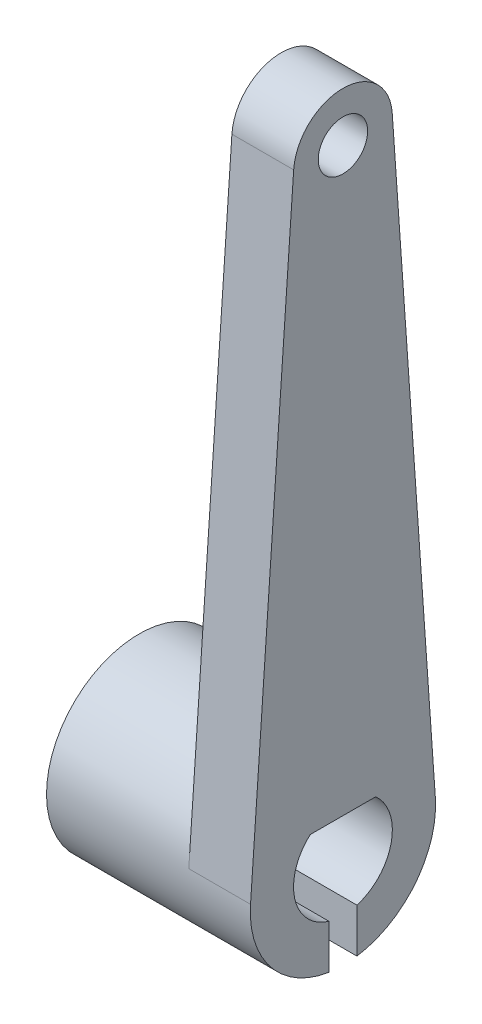
SolidWorks part; units mm, degrees
ref_plane "Front Plane" through (0, 0, 0) normal (0, 0, 1) x (1, 0, 0)
ref_plane "Top Plane" through (0, 0, 0) normal (0, 1, 0) x (1, 0, 0)
ref_plane "Right Plane" through (0, 0, 0) normal (1, 0, 0) x (0, 0, -1)
sketch "Sketch2" plane through (0, 0, 0) normal (1, 0, 0) x (0, 0, -1)
  line L0 (-2.6458, 3) -> (2.6458, 3)
  line L1 (-7.4816, 0.525) -> (-3.9902, 50.28)
  line L3 (3.9902, 50.28) -> (7.4816, 0.525)
  arc A0 (-2.6458, 3) -> (2.6458, 3) centre (0, 0) ccw
  arc A1 (-7.4816, 0.525) -> (7.4816, 0.525) centre (0, 0) ccw
  arc A2 (3.9902, 50.28) -> (-3.9902, 50.28) centre (0, 50) ccw
  circle A3 centre (0, 50) radius 2
  dimension "D1" = 8
  dimension "D2" = 7
  dimension "D3" = 15
  dimension "D4" = 8
  dimension "D6" = 4
  dimension "D5" = 50
extrude "Boss-Extrude1" add sketch "Sketch2" along normal blind 2.5 and the other way blind 2.5 contours L3 A2 L1 A1 A3 A0 L0 region at (0, 21.1681, 0)
sketch "Sketch3" plane through (2.5, 0, 0) normal (1, 0, 0) x (0, 0, -1)
  line L1 (-1.132, -11.1635) -> (1.132, -11.1635)
  line L2 (-1.132, -11.1635) -> (-1.132, -3.8365)
  line L3 (-1.132, -3.8365) -> (1.132, -3.8365)
  line L4 (1.132, -11.1635) -> (1.132, -3.8365)
  line L5 (-1.132, -11.1635) -> (1.132, -3.8365) construction
  line L6 (-1.132, -3.8365) -> (1.132, -11.1635) construction
  arc A0 (-7.4816, 0.525) -> (7.4816, 0.525) centre (0, 0) ccw construction
  arc A1 (-2.6458, 3) -> (2.6458, 3) centre (0, 0) ccw construction
  point P0 (0, -7.5)
extrude "Cut-Extrude1" cut sketch "Sketch3" against normal up to next
chamfer "Chamfer1" [suppressed] distance 0.5 angle 45
sketch "Sketch5" plane through (-2.5, 0, 0) normal (-1, 0, 0) x (0, 0, 1)
  line L5 (-1.132, -7.4141) -> (-1.132, -3.8365)
  line L6 (-2.6458, 3) -> (2.6458, 3)
  line L7 (1.132, -3.8365) -> (1.132, -7.4141)
  line L8 (7.4816, 0.525) -> (3.9902, 50.28)
  line L9 (-3.9902, 50.28) -> (-7.4816, 0.525)
  line L10 (-1.132, -7.4141) -> (-1.132, -3.8365)
  line L11 (-2.6458, 3) -> (2.6458, 3)
  line L12 (1.132, -3.8365) -> (1.132, -7.4141)
  circle A0 centre (0, 0) radius 7.5
  arc A5 (-7.4816, 0.525) -> (-1.132, -7.4141) centre (0, 0) ccw
  arc A6 (-2.6458, 3) -> (-1.132, -3.8365) centre (0, 0) ccw
  arc A7 (1.132, -3.8365) -> (2.6458, 3) centre (0, 0) ccw
  arc A8 (1.132, -7.4141) -> (7.4816, 0.525) centre (0, 0) ccw
  arc A9 (3.9902, 50.28) -> (-3.9902, 50.28) centre (0, 50) ccw
  arc A10 (-7.4816, 0.525) -> (-1.132, -7.4141) centre (0, 0) ccw
  arc A11 (-2.6458, 3) -> (-1.132, -3.8365) centre (0, 0) ccw
  arc A12 (1.132, -3.8365) -> (2.6458, 3) centre (0, 0) ccw
  arc A13 (1.132, -7.4141) -> (7.4816, 0.525) centre (0, 0) ccw
  arc M12 (-7.4816, 0.525) -> (-1.132, -7.4141) centre (0, 0) ccw
  line M13 (-1.132, -7.4141) -> (-1.132, -3.8365)
  arc M14 (-1.132, -3.8365) -> (-2.6458, 3) centre (0, 0) cw
  line M15 (-2.6458, 3) -> (2.6458, 3)
  arc M16 (2.6458, 3) -> (1.132, -3.8365) centre (0, 0) cw
  line M17 (1.132, -3.8365) -> (1.132, -7.4141)
  arc M18 (1.132, -7.4141) -> (7.4816, 0.525) centre (0, 0) ccw
  dimension "D1" = 0
extrude "Boss-Extrude2" add sketch "Sketch5" along normal offset from surface (11.5 mm away) 16.5 contours A0 M18 M12 M13 M14 M15 M16 M17 region at (-2.5, -4.5524, -5.6919) up to face at (2.5, 8.5456, 0)
